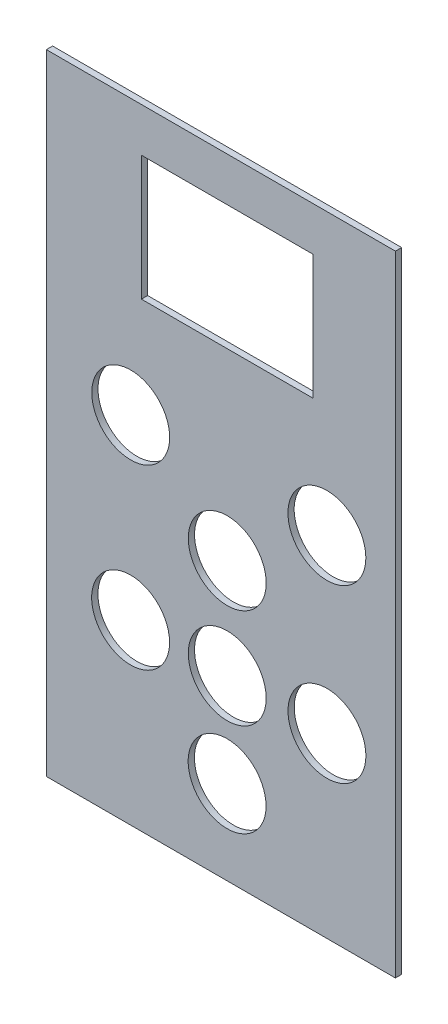
SolidWorks part; units mm, degrees
ref_plane "前视基准面" through (0, 0, 0) normal (0, 0, 1) x (1, 0, 0)
ref_plane "上视基准面" through (0, 0, 0) normal (0, 1, 0) x (1, 0, 0)
ref_plane "右视基准面" through (0, 0, 0) normal (1, 0, 0) x (0, 0, -1)
sketch "草图1" plane through (0, 0, 0) normal (0, 0, 1) x (1, 0, 0)
  line L0 (53.3883, -2.9399) -> (25.8883, -2.9399)
  line L1 (10.6383, 4.1061) -> (66.6383, 4.1061)
  line L2 (10.6383, 4.1061) -> (10.6383, -96.8939)
  line L3 (10.6383, -96.8939) -> (66.6383, -96.8939)
  line L4 (66.6383, 4.1061) -> (66.6383, -96.8939)
  line L5 (53.3883, -2.9399) -> (53.3883, -22.9399)
  line L6 (53.3883, -22.9399) -> (25.8883, -22.9399)
  line L7 (25.8883, -2.9399) -> (25.8883, -22.9399)
  circle A0 centre (39.6383, -83.3939) radius 6.25
  circle A1 centre (39.6556, -68.3939) radius 6.25
  circle A2 centre (24.1557, -68.3939) radius 6.25
  circle A3 centre (55.6555, -68.3939) radius 6.25
  circle A4 centre (39.6593, -52.3939) radius 6.25
  circle A5 centre (55.6463, -40.8939) radius 6.25
  circle A6 centre (24.1709, -39.8939) radius 6.25
  point P22 (0, 0)
  point P23 (0, 0)
  dimension "D3" = 28.5
  dimension "D4" = 28.5
  dimension "D5" = 73.954
  dimension "D18" = 27.5
  dimension "D1" = 56
  dimension "D2" = 101
  dimension "D10" = 15
  dimension "D11" = 16
  dimension "D14" = 27.5
  dimension "D15" = 28.5
  dimension "D16" = 29
  dimension "D17" = 13.5
  dimension "D19" = 20
  dimension "D20" = 15.25
extrude "凸台-拉伸1" add sketch "草图1" along normal blind 1
